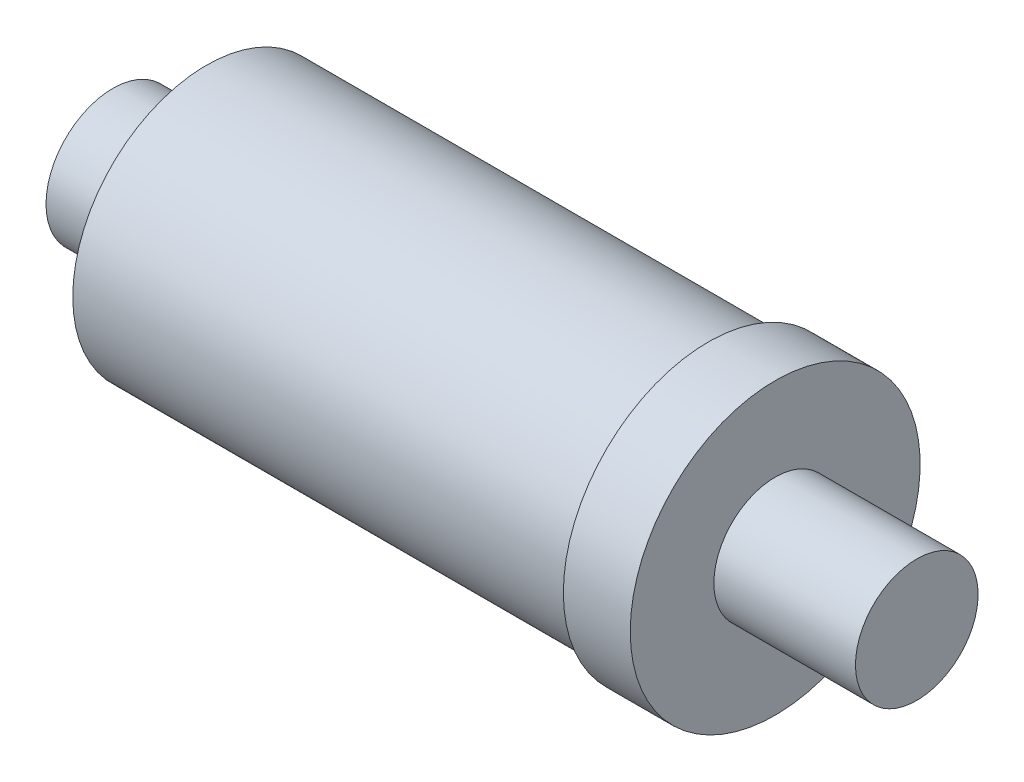
SolidWorks part; units mm, degrees
ref_plane "Front Plane" through (0, 0, 0) normal (0, 0, 1) x (1, 0, 0)
ref_plane "Top Plane" through (0, 0, 0) normal (0, 1, 0) x (1, 0, 0)
ref_plane "Right Plane" through (0, 0, 0) normal (1, 0, 0) x (0, 0, -1)
sketch "Sensor_Turck Sketch" plane through (0, 0, 0) normal (0, 0, 1) x (1, 0, 0)
  line L0 (-1000, 0) -> (1000, 0) construction
  line L1 (12.7, 0) -> (12.7, 5.5)
  line L2 (12.7, 5.5) -> (0, 5.5)
  line L3 (0, 5.5) -> (0, 13)
  line L4 (0, 13) -> (-6, 13)
  line L5 (-6, 13) -> (-6, 12)
  line L6 (-6, 12) -> (-51, 12)
  line L7 (-51, 12) -> (-51, 6)
  line L8 (-51, 6) -> (-59.4, 6)
  line L9 (-59.4, 6) -> (-59.4, 0)
  line L10 (-59.4, 0) -> (12.7, 0)
revolve "Sensor_Turck" add sketch "Sensor_Turck Sketch" angle 360 about L0
ref_axis "Engine Axis" through (16.305, 0, 0) along (-1, 0, 0)
